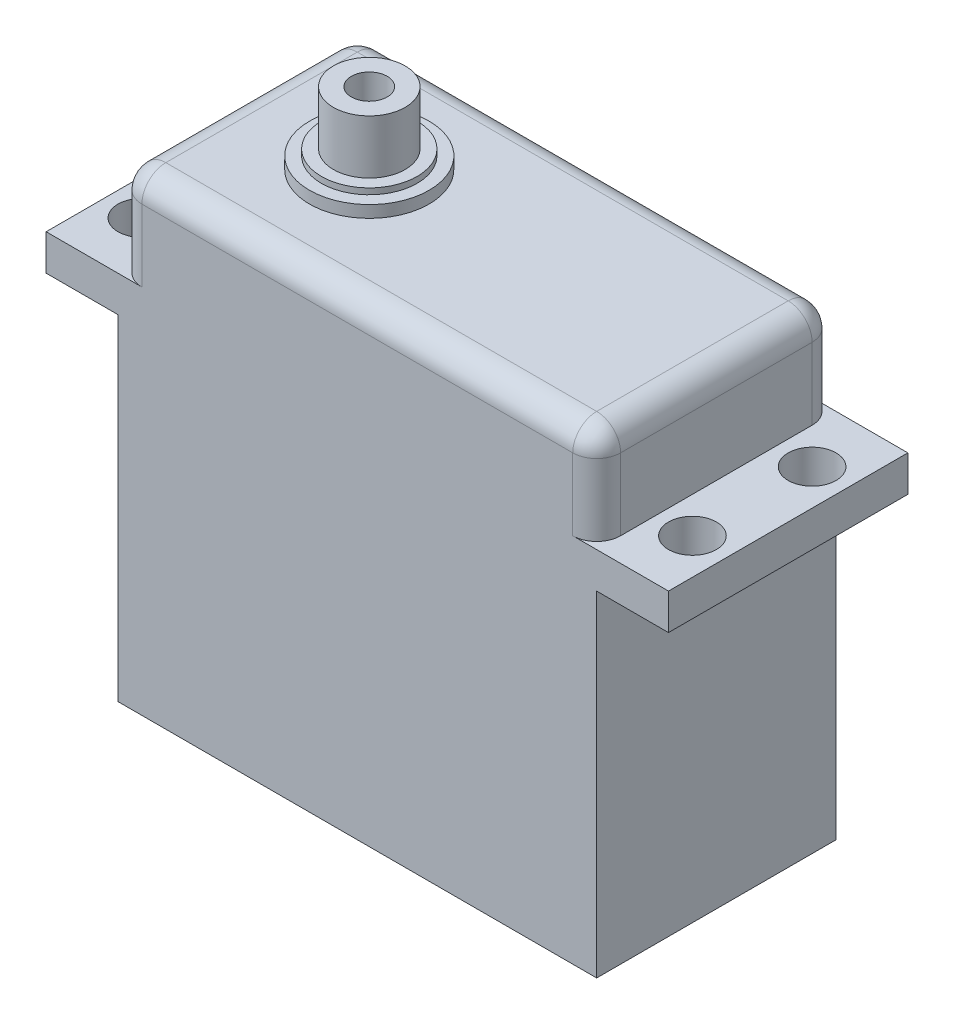
SolidWorks part; units mm, degrees
ref_plane "前视基准面" through (0, 0, 0) normal (0, 0, 1) x (1, 0, 0)
ref_plane "上视基准面" through (0, 0, 0) normal (0, 1, 0) x (1, 0, 0)
ref_plane "右视基准面" through (0, 0, 0) normal (1, 0, 0) x (0, 0, -1)
other "Configuration Table"
sketch "草图2" plane through (0, 0, 0) normal (0, 0, 1) x (1, 0, 0)
  line L1 (-21.3142, 15.5031) -> (18.6858, 15.5031)
  line L2 (-21.3142, 15.5031) -> (-21.3142, -23.4969)
  line L3 (-21.3142, -23.4969) -> (18.6858, -23.4969)
  line L4 (18.6858, 15.5031) -> (18.6858, -23.4969)
  line L5 (-21.3142, 15.5031) -> (18.6858, -23.4969) construction
  line L6 (-21.3142, -23.4969) -> (18.6858, 15.5031) construction
  point P0 (-1.3142, -3.9969)
  dimension "D1" = 40
  dimension "D2" = 39
extrude "凸台-拉伸1" add sketch "草图2" along normal blind 20
sketch "草图3" plane through (18.6858, 0, 0) normal (1, 0, 0) x (0, 0, -1)
  line L0 (-20, -23.4969) -> (-20, 7.5024)
  line L1 (-20, -23.4969) -> (-20, 15.5031) construction
  line L2 (-20, 7.5024) -> (0, 7.5024)
  line L3 (0, -23.4969) -> (0, 15.5031) construction
  line L4 (0, 7.5024) -> (0, 4.4982)
  line L5 (0, 4.4982) -> (-20, 4.4982)
  line M1 (0, -23.4969) -> (0, 15.5031)
  line M3 (-20, 15.5031) -> (-20, -23.4969)
extrude "凸台-拉伸3" add sketch "草图3" along normal blind 6 contours L5 L2 M1 M3 region at (18.6858, 6.0003, 10)
sketch "草图5" plane through (-21.3142, 0, 0) normal (-1, 0, 0) x (0, 0, 1)
  line L0 (0, -23.4969) -> (0, 7.5031)
  line L1 (0, 15.5031) -> (0, -23.4969) construction
  line L2 (0, 7.5031) -> (20, 7.5024)
  line L3 (20, 7.5024) -> (20, 4.5024)
  line L4 (20, 15.5031) -> (20, -23.4969) construction
  line L5 (20, 4.5024) -> (0, 4.5024)
  line M3 (0, 15.5031) -> (0, -23.4969)
  line M5 (20, -23.4969) -> (20, 15.5031)
  dimension "D1" = 31
  dimension "D2" = 3
extrude "凸台-拉伸4" add sketch "草图5" along normal blind 6 contours L5 L2 M5 M3 region at (-21.3142, 6.0026, 9.9996)
sketch "草图6" plane through (0, 7.5024, 0) normal (0, 1, 0) x (1, 0, 0)
  circle A0 centre (21.6858, -15) radius 2
  circle A1 centre (21.6858, -5) radius 2
  circle A2 centre (-24.3142, -15) radius 2
  circle A3 centre (-24.3142, -5) radius 2
  dimension "D2" = 4
  dimension "D4" = 4
  dimension "D3" = 4
  dimension "D6" = 4
extrude "切除-拉伸7" cut sketch "草图6" against normal mid plane 9
sketch "草图11" plane through (0, 15.5031, 0) normal (0, 1, 0) x (1, 0, 0)
  circle A0 centre (-10.3142, -10) radius 5
  dimension "D2" = 10
extrude "凸台-拉伸5" add sketch "草图11" along normal blind 1
sketch "草图12" plane through (0, 16.5031, 0) normal (0, 1, 0) x (1, 0, 0)
  circle A0 centre (-10.3142, -10) radius 4
  dimension "D1" = 8
extrude "凸台-拉伸6" add sketch "草图12" along normal blind 0.5
sketch "草图13" plane through (0, 17.0031, 0) normal (0, 1, 0) x (1, 0, 0)
  circle A0 centre (-10.3142, -10) radius 3
  dimension "D1" = 6
extrude "凸台-拉伸7" add sketch "草图13" along normal blind 4.5
sketch "草图14" plane through (0, 21.5031, 0) normal (0, 1, 0) x (1, 0, 0)
  circle A0 centre (-10.3142, -10) radius 1.5
  dimension "D1" = 3
extrude "切除-拉伸8" cut sketch "草图14" against normal mid plane 15.5
fillet "圆角8" radius 2 8 edges at (-21.3142, 15.5031, 10) (-21.3142, 11.5027, 20) (-21.3142, 11.5031, 0) (-1.3142, 15.5031, 0) (18.6858, 11.5027, 0) (18.6858, 15.5031, 10) (18.6858, 11.5027, 20) (-1.3142, 15.5031, 20)
